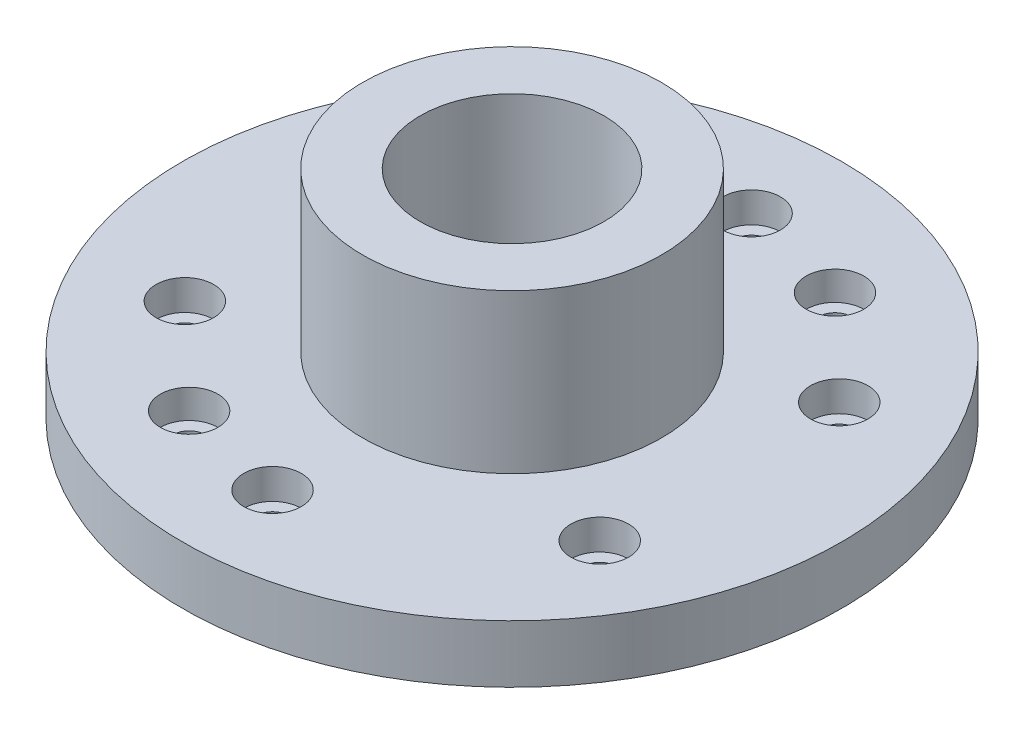
SolidWorks part; units mm, degrees
ref_plane "Front Plane" through (0, 0, 0) normal (0, 0, 1) x (1, 0, 0)
ref_plane "Top Plane" through (0, 0, 0) normal (0, 1, 0) x (1, 0, 0)
ref_plane "Right Plane" through (0, 0, 0) normal (1, 0, 0) x (0, 0, -1)
ref_axis "Axis1" through (0, -55, 0) along (0, 1, 0)
sketch "Sketch1" plane through (0, 0, 0) normal (1, 0, 0) x (0, 0, -1)
  line L0 (-12.75, 0) -> (-45.75, 0)
  line L1 (-45.75, 0) -> (-45.75, 8)
  line L2 (-45.75, 8) -> (-20.75, 8)
  line L3 (-20.75, 8) -> (-20.75, 30)
  line L4 (-20.75, 30) -> (-12.75, 30)
  line L5 (-12.75, 30) -> (-12.75, 0)
  dimension "D1" = 12.75
  dimension "D2" = 8
  dimension "D3" = 8
  dimension "D4" = 30
  dimension "D5" = 25
revolve "Revolve1" add sketch "Sketch1" angle 360 about axis through (0, -55, 0) along (0, 1, 0)
sketch "Sketch4" plane through (0, 8, 0) normal (0, 1, 0) x (1, 0, 0)
  line L0 (0, 0) -> (0, 66.5) construction
  line L1 (0, 0) -> (63.9207, 0) construction
  line L3 (0, 0) -> (28.7953, 16.625) construction
  circle A0 centre (0, 0) radius 33.25 construction
  circle A2 centre (0, 0) radius 20.75 construction
  point P31 (0, 0)
  point P35 (0, 33.25)
  point P39 (28.7953, 16.625)
  point P40 (28.7953, -16.625)
  point P41 (0, -33.25)
  point P42 (-28.7953, -16.625)
  point P43 (-28.7953, 16.625)
  point P44 (0, 0)
  dimension "D1" = 12.5
  dimension "D3" = 30
  dimension "D2" = 6
sketch "Sketch10" plane through (0, 8, 0) normal (0, 1, 0) x (1, 0, 0)
  point P0 (0, 33.25)
  point P3 (28.7953, 16.625)
  point P6 (28.7953, -16.625)
  point P9 (0, -33.25)
  point P12 (-28.7953, -16.625)
  point P15 (-28.7953, 16.625)
hole_wizard "CBORE for M4 SHCS3" positions "Sketch10" profile "Sketch11" counterbore size "M4" standard "ANSI Metric" end condition through all
sketch "Sketch11" plane through (0, 8, -33.25) normal (1, 0, 0) x (0, 0, 1)
  line L0 (0, 0) -> (0, 8)
  line L1 (0, 8) -> (2.25, 8)
  line L3 (2.25, 8) -> (2.25, 4.2)
  line L4 (2.25, 4.2) -> (4, 4.2)
  line L5 (4, 4.2) -> (4, 0)
  line L7 (4, 0) -> (0, 0)
  line L11 (0, -6.35) -> (0, 107.95) construction
  dimension "Thru Hole Dia." = 4.5
  dimension "Thru Hole Depth" = 8
  dimension "C'Bore Dia." = 8
  dimension "C'Bore Depth" = 4.2
sketch "Sketch13" plane through (0, 8, 0) normal (0, 1, 0) x (1, 0, 0)
  circle A0 centre (0, 0) radius 33.25
  point P4 (-15.3132, -29.5139)
  point P5 (15.3132, 29.5139)
hole_wizard "CBORE for M4 SHCS4" positions "Sketch13" profile "Sketch14" counterbore size "M4" standard "ANSI Metric" end condition through all
sketch "Sketch14" plane through (15.3132, 8, -29.5139) normal (1, 0, 0) x (0, 0, 1)
  line L0 (0, 0) -> (0, 8)
  line L1 (0, 8) -> (2.25, 8)
  line L3 (2.25, 8) -> (2.25, 4)
  line L4 (2.25, 4) -> (4, 4)
  line L5 (4, 4) -> (4, 0)
  line L7 (4, 0) -> (0, 0)
  line L11 (0, -6.35) -> (0, 107.95) construction
  dimension "Thru Hole Dia." = 4.5
  dimension "Thru Hole Depth" = 8
  dimension "C'Bore Dia." = 8
  dimension "C'Bore Depth" = 4
